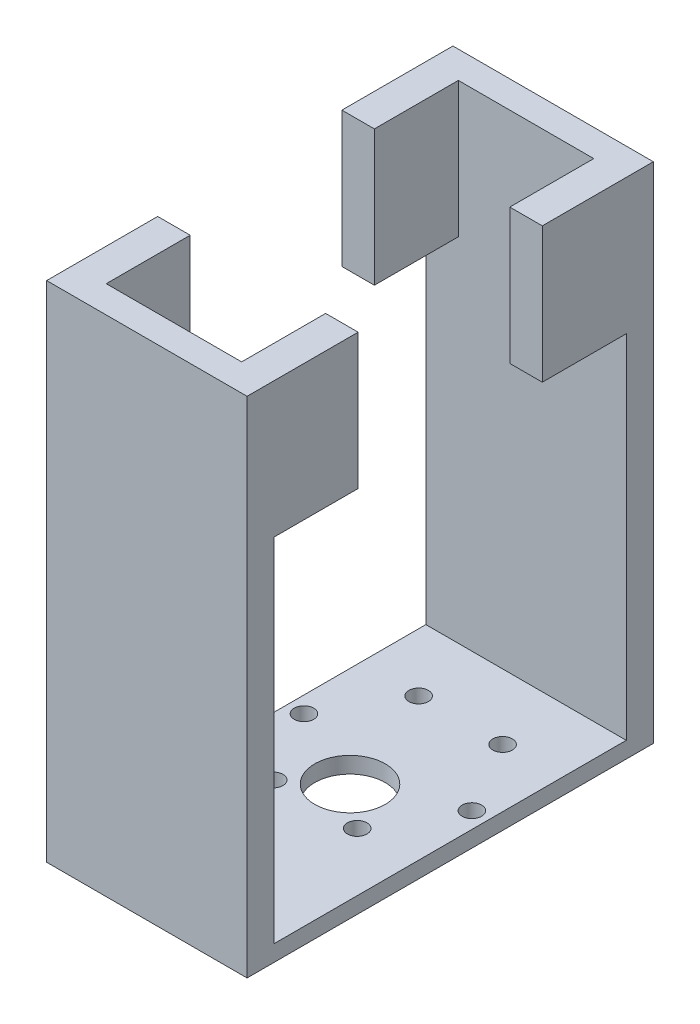
SolidWorks part; units mm, degrees
ref_plane "Front Plane" through (0, 0, 0) normal (0, 0, 1) x (1, 0, 0)
ref_plane "Top Plane" through (0, 0, 0) normal (0, 1, 0) x (1, 0, 0)
ref_plane "Right Plane" through (0, 0, 0) normal (1, 0, 0) x (0, 0, -1)
sketch "Sketch2" plane through (0, 0, 0) normal (0, 1, 0) x (1, 0, 0)
  line L1 (7.75, -13.4234) -> (15.5, 0) construction
  line L2 (15.5, 0) -> (7.75, 13.4234) construction
  line L3 (7.75, 13.4234) -> (-7.75, 13.4234) construction
  line L4 (-7.75, 13.4234) -> (-15.5, 0) construction
  line L5 (-15.5, 0) -> (-7.75, -13.4234) construction
  line L6 (-7.75, -13.4234) -> (7.75, -13.4234) construction
  circle A0 centre (0, 0) radius 13.4234 construction
  circle A1 centre (-15.5, 0) radius 1.8
  circle A2 centre (-7.75, 13.4234) radius 1.8
  circle A3 centre (7.75, 13.4234) radius 1.8
  circle A4 centre (15.5, 0) radius 1.8
  circle A5 centre (7.75, -13.4234) radius 1.8
  circle A6 centre (-7.75, -13.4234) radius 1.8
  circle A7 centre (0, 0) radius 18.5
  dimension "D2" = 3.6
  dimension "D3" = 37
  dimension "D1" = 31
extrude "Boss-Extrude1" add sketch "Sketch2" along normal blind 3
sketch "Sketch3" plane through (0, 3, 0) normal (0, 1, 0) x (1, 0, 0)
  line L0 (0, 0) -> (0, -7) construction
  circle A0 centre (0, -7) radius 6.5
  dimension "D2" = 13
  dimension "D1" = 7
extrude "Cut-Extrude1" cut sketch "Sketch3" against normal blind 3
sketch "Sketch4" plane through (0, 3, 0) normal (0, 1, 0) x (1, 0, 0)
  line L1 (-18.5, 30.5) -> (18.5, 30.5)
  line L4 (-18.5, -44.5) -> (18.5, -44.5)
  line L6 (-18.5, -44.5) -> (-18.5, 30.5)
  line L7 (18.5, 30.5) -> (18.5, -44.5)
  line L8 (0, -7) -> (2.9813, -7) construction
  circle A1 centre (0, 0) radius 18.5
  circle A2 centre (0, 0) radius 18.5
  point P7 (18.5, -7)
  circle M11 centre (0, 0) radius 18.5
  dimension "D2" = 75
  dimension "D1" = 0
extrude "Boss-Extrude2" add sketch "Sketch4" against normal up to surface (3 mm away) contours L7 L1 L6 M11 | L7 L6 L4 M11 region at (0, 3, -21.9811) region at (0, 3, 29.2305) up to face at (0, 0, 13.5)
sketch "Sketch5" plane through (0, 3, 0) normal (0, 1, 0) x (1, 0, 0)
  line L0 (18.5, 30.5) -> (18.5, -44.5) construction
  line L1 (-18.5, 30.5) -> (18.5, 30.5)
  line L2 (-18.5, 30.5) -> (-18.5, 25.5)
  line L3 (-18.5, 25.5) -> (18.5, 25.5)
  line L4 (18.5, 30.5) -> (18.5, 25.5)
  line L6 (-18.5, -44.5) -> (18.5, -44.5)
  line L7 (-18.5, -44.5) -> (-18.5, -39.5)
  line L8 (-18.5, -39.5) -> (18.5, -39.5)
  line L9 (18.5, -44.5) -> (18.5, -39.5)
  dimension "D1" = 5
extrude "Boss-Extrude3" add sketch "Sketch5" along normal blind 70
sketch "Sketch6" plane through (0, 73, 0) normal (0, 1, 0) x (1, 0, 0)
  line L0 (18.5, 25.5) -> (18.5, -39.5) construction
  line L1 (-18.5, 25.5) -> (18.5, 25.5)
  line L2 (-18.5, 25.5) -> (-18.5, 10)
  line L3 (-18.5, 10) -> (18.5, 10)
  line L4 (18.5, 25.5) -> (18.5, 10)
  line L6 (-18.5, -39.5) -> (18.5, -39.5)
  line L7 (-18.5, -39.5) -> (-18.5, -24)
  line L8 (-18.5, -24) -> (18.5, -24)
  line L9 (18.5, -39.5) -> (18.5, -24)
  dimension "D1" = 34
extrude "Boss-Extrude4" add sketch "Sketch6" against normal blind 5
sketch "Sketch7" plane through (0, 73, 0) normal (0, 1, 0) x (1, 0, 0)
  line L0 (18.5, 30.5) -> (-18.5, 30.5) construction
  line L1 (-18.5, 10) -> (-12.5, 10)
  line L2 (-18.5, 10) -> (-18.5, 30.5)
  line L3 (-18.5, 30.5) -> (-12.5, 30.5)
  line L4 (-12.5, 10) -> (-12.5, 30.5)
  line L5 (18.5, 10) -> (12.5, 10)
  line L6 (18.5, 10) -> (18.5, 30.5)
  line L7 (18.5, 30.5) -> (12.5, 30.5)
  line L8 (12.5, 10) -> (12.5, 30.5)
  line L9 (-18.5, -24) -> (-12.5, -24)
  line L10 (-18.5, -24) -> (-18.5, -44.5)
  line L11 (-18.5, -44.5) -> (-12.5, -44.5)
  line L12 (-12.5, -24) -> (-12.5, -44.5)
  line L13 (18.5, -24) -> (12.5, -24)
  line L14 (18.5, -24) -> (18.5, -44.5)
  line L15 (18.5, -44.5) -> (12.5, -44.5)
  line L16 (12.5, -24) -> (12.5, -44.5)
  dimension "D1" = 25
extrude "Boss-Extrude5" add sketch "Sketch7" along normal blind 20
sketch "Sketch8" plane through (0, 73, 0) normal (0, 1, 0) x (1, 0, 0)
  line L0 (-12.5, 10) -> (-12.5, 25.5)
  line L1 (-12.5, 10) -> (-12.5, 30.5) construction
  line L2 (-12.5, 25.5) -> (12.5, 25.5)
  line L3 (12.5, 30.5) -> (12.5, 10) construction
  line L4 (12.5, 25.5) -> (12.5, 10)
  line L5 (12.5, 10) -> (-12.5, 10)
  line L6 (-12.5, -24) -> (12.5, -24)
  line L7 (12.5, -24) -> (12.5, -39.5)
  line L8 (12.5, -24) -> (12.5, -44.5) construction
  line L9 (12.5, -39.5) -> (-12.5, -39.5)
  line L10 (-12.5, -44.5) -> (-12.5, -24) construction
  line L11 (-12.5, -39.5) -> (-12.5, -24)
  line L12 (-18.5, 25.5) -> (18.5, 25.5) construction
  line L13 (18.5, -39.5) -> (-18.5, -39.5) construction
extrude "Cut-Extrude2" cut sketch "Sketch8" against normal blind 10
sketch "Sketch9" plane through (0, 73, 0) normal (0, 1, 0) x (1, 0, 0)
  line L0 (12.5, 30.5) -> (12.5, 10) construction
  line L1 (-12.5, 30.5) -> (12.5, 30.5)
  line L2 (-12.5, 30.5) -> (-12.5, 25.5)
  line L3 (-12.5, 25.5) -> (12.5, 25.5)
  line L4 (12.5, 30.5) -> (12.5, 25.5)
  line L5 (-18.5, 25.5) -> (18.5, 25.5) construction
  line L7 (-12.5, -39.5) -> (12.5, -39.5)
  line L8 (-12.5, -39.5) -> (-12.5, -44.5)
  line L9 (-12.5, -44.5) -> (12.5, -44.5)
  line L10 (12.5, -39.5) -> (12.5, -44.5)
extrude "Boss-Extrude6" add sketch "Sketch9" along normal up to surface (20 mm away) up to face at (-15.5, 93, -20.25)
